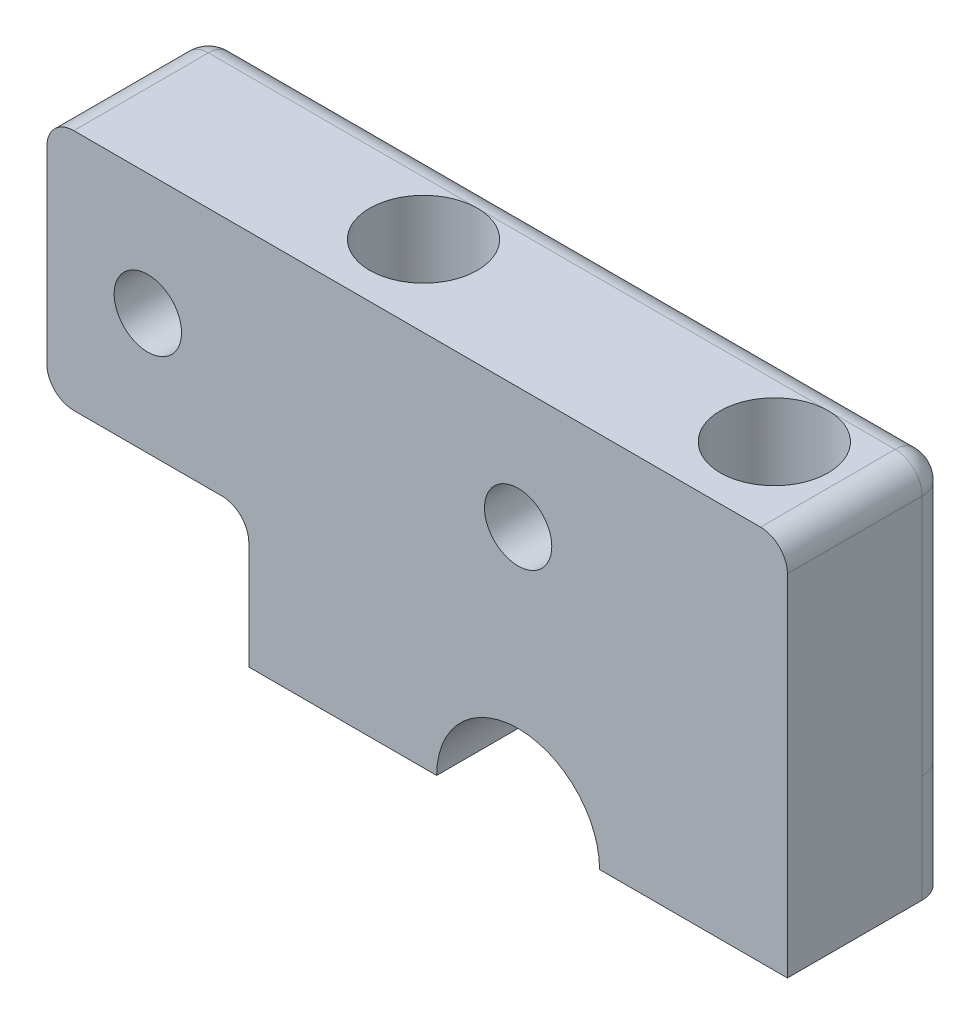
SolidWorks part; units mm, degrees
ref_plane "Plan de face" through (0, 0, 0) normal (0, 0, 1) x (1, 0, 0)
ref_plane "Plan de dessus" through (0, 0, 0) normal (0, 1, 0) x (1, 0, 0)
ref_plane "Plan de droite" through (0, 0, 0) normal (1, 0, 0) x (0, 0, -1)
sketch "Esquisse1" plane through (0, 0, 0) normal (0, 0, 1) x (1, 0, 0)
  line L1 (-16.8144, 9.7258) -> (23.1856, 9.7258)
  line L2 (-16.8144, 9.7258) -> (-16.8144, -8.2742)
  line L3 (-16.8144, -8.2742) -> (23.1856, -8.2742)
  line L4 (23.1856, 9.7258) -> (23.1856, -8.2742)
  dimension "D1" = 40
  dimension "D2" = 18
extrude "Boss.-Extru.1" add sketch "Esquisse1" along normal blind 12
sketch "Esquisse2" plane through (0, -8.2742, 0) normal (0, -1, 0) x (1, 0, 0)
  line L1 (23.1856, 0) -> (-16.8144, 0)
  line L2 (23.1856, 0) -> (23.1856, 12)
  line L3 (23.1856, 12) -> (-16.8144, 12)
  line L4 (-16.8144, 0) -> (-16.8144, 12)
extrude "Boss.-Extru.2" add sketch "Esquisse2" along normal blind 10
sketch "Esquisse3" plane through (0, 0, 12) normal (0, 0, 1) x (1, 0, 0)
  line L0 (3.1856, -18.2742) -> (3.1856, 9.7258) construction
  line L1 (23.1856, -18.2742) -> (-16.8144, -18.2742) construction
  line L2 (23.1856, 9.7258) -> (-16.8144, 9.7258) construction
  line L3 (-2.8644, -18.2742) -> (9.2356, -18.2742)
  arc A0 (-2.8644, -18.2742) -> (9.2356, -18.2742) centre (3.1856, -18.2742) cw
  dimension "D1" = 6.05
extrude "Enlèv. mat.-Extru.1" cut sketch "Esquisse3" against normal up to vertex (12 mm away) up to point (-16.8144, -18.2742, 0)
sketch "Esquisse4" plane through (0, -18.2742, 0) normal (0, -1, 0) x (1, 0, 0)
  line L0 (9.2356, 12) -> (23.1856, 0) construction
  line L1 (-2.8644, 0) -> (-16.8144, 12) construction
  circle A0 centre (-9.8394, 6) radius 2.5
  circle A1 centre (16.2106, 6) radius 2.5
  dimension "D1" = 5
  dimension "D2" = 5
extrude "Enlèv. mat.-Extru.2" cut sketch "Esquisse4" against normal up to vertex (28 mm away) up to point (23.1856, 9.7258, 12)
sketch "Esquisse5" plane through (0, 0, 12) normal (0, 0, 1) x (1, 0, 0)
  line L0 (23.1856, 0.7258) -> (-16.8144, 0.7258) construction
  line L1 (23.1856, -18.2742) -> (23.1856, 9.7258) construction
  line L2 (-16.8144, 9.7258) -> (-16.8144, -18.2742) construction
  line L3 (23.1856, 9.7258) -> (-16.8144, 9.7258) construction
  circle A1 centre (3.1856, 0.7258) radius 2.5
  dimension "D1" = 9
extrude "Enlèv. mat.-Extru.3" cut sketch "Esquisse5" against normal up to vertex (12 mm away) up to point (-16.8144, 9.7258, 0)
sketch "Esquisse6" plane through (0, 9.7258, 0) normal (0, 1, 0) x (1, 0, 0)
  circle A0 centre (16.2106, -6) radius 4
  circle A1 centre (-9.8394, -6) radius 4
  dimension "D1" = 8
extrude "Enlèv. mat.-Extru.5" cut sketch "Esquisse6" against normal blind 12
sketch "Esquisse7" plane through (-16.8144, 0, 0) normal (-1, 0, 0) x (0, 0, 1)
  line L0 (12, 9.7258) -> (12, -18.2742) construction
  line L1 (0, 9.7258) -> (12, 9.7258)
  line L2 (0, 9.7258) -> (0, -8.2742)
  line L3 (0, -8.2742) -> (12, -8.2742)
  line L4 (12, 9.7258) -> (12, -8.2742)
  dimension "D1" = 18
extrude "Boss.-Extru.3" add sketch "Esquisse7" along normal blind 15
sketch "Esquisse8" plane through (23.1856, 0, 0) normal (1, 0, 0) x (0, 0, -1)
  line L0 (-12, -18.2742) -> (-12, 9.7258) construction
  line L1 (0, 9.7258) -> (-12, 9.7258)
  line L2 (0, 9.7258) -> (0, -8.2742)
  line L3 (0, -8.2742) -> (-12, -8.2742)
  line L4 (-12, 9.7258) -> (-12, -8.2742)
  dimension "D1" = 18
extrude "Boss.-Extru.4" add sketch "Esquisse8" along normal blind 15
sketch "Esquisse9" plane through (0, 0, 12) normal (0, 0, 1) x (1, 0, 0)
  line L0 (30.6856, -8.2742) -> (30.6856, 9.7258) construction
  line L1 (38.1856, -8.2742) -> (23.1856, -8.2742) construction
  line L2 (38.1856, 9.7258) -> (-31.8144, 9.7258) construction
  line L3 (-24.3144, -8.2742) -> (-24.3144, 9.7258) construction
  line L4 (-31.8144, -8.2742) -> (-16.8144, -8.2742) construction
  circle A0 centre (-24.3144, 0.7258) radius 2.5
  circle A1 centre (30.6856, 0.7258) radius 2.5
  circle A2 centre (3.1856, 0.7258) radius 2.5 construction
extrude "Enlèv. mat.-Extru.6" cut sketch "Esquisse9" against normal up to vertex (12 mm away) up to point (-31.8144, 9.7258, 0)
fillet "Congé1" radius 2 13 edges at (-31.8144, 0.7258, 0) (38.1856, 0.7258, 0) (3.1856, 9.7258, 0) (23.1856, -8.2742, 6) (38.1856, -8.2742, 6) (38.1856, 9.7258, 6) (-31.8144, 9.7258, 6) (-31.8144, -8.2742, 6) (-16.8144, -8.2742, 6) (23.1856, -13.2742, 0) (-16.8144, -13.2742, 0) (30.6856, -8.2742, 0) (-24.3144, -8.2742, 0)
sketch "Esquisse11" plane through (0, -8.2742, 0) normal (0, -1, 0) x (1, 0, 0)
  line L0 (38.1856, 12) -> (38.1856, 2) construction
  line L1 (23.1856, 13.8246) -> (38.1856, 13.8246)
  line L2 (23.1856, 13.8246) -> (23.1856, -2.8739)
  line L3 (23.1856, -2.8739) -> (38.1856, -2.8739)
  line L4 (38.1856, 13.8246) -> (38.1856, -2.8739)
  line L5 (23.1856, 2) -> (23.1856, 12) construction
extrude "Enlèv. mat.-Extru.7" cut sketch "Esquisse11" against normal blind 27 and the other way blind 10
fillet "Congé2" radius 2 3 edges at (23.1856, 9.7258, 7) (23.1856, 9.1401, 0.5858) (23.1856, 0.4579, 0)
